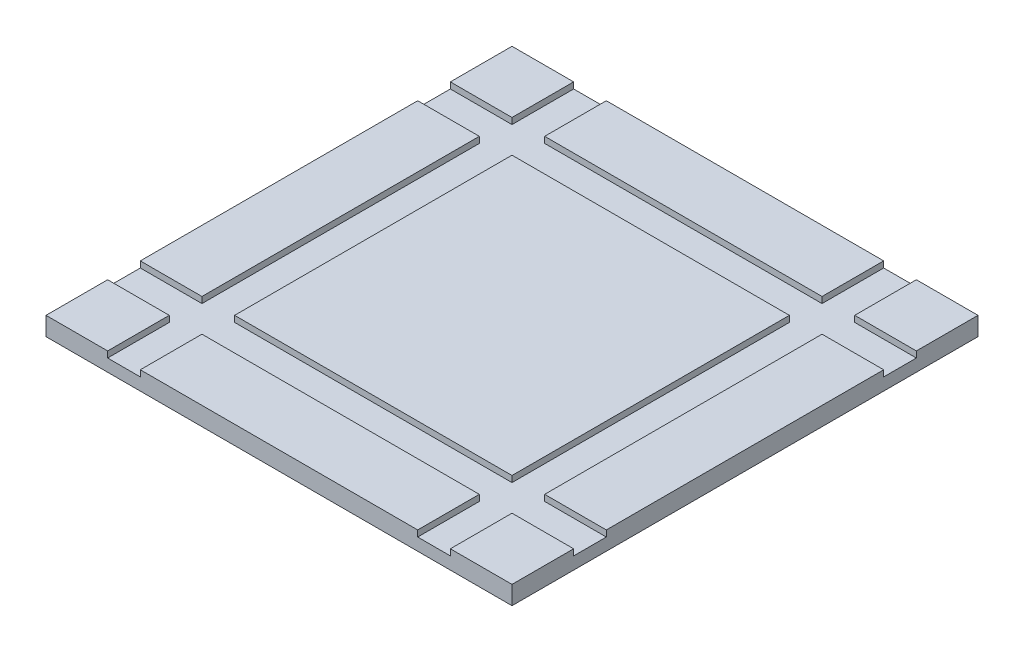
SolidWorks part; units mm, degrees
ref_plane "Front Plane" through (0, 0, 0) normal (0, 0, 1) x (1, 0, 0)
ref_plane "Top Plane" through (0, 0, 0) normal (0, 1, 0) x (1, 0, 0)
ref_plane "Right Plane" through (0, 0, 0) normal (1, 0, 0) x (0, 0, -1)
sketch "Sketch1" plane through (0, 0, 0) normal (0, 1, 0) x (1, 0, 0)
  line L0 (-37.8, 22.5) -> (-37.8, 27.8)
  line L5 (-37.8, 37.8) -> (-27.8, 37.8)
  line L6 (-37.8, 37.8) -> (-37.8, 27.8)
  line L7 (-37.8, 27.8) -> (-27.8, 27.8)
  line L8 (-27.8, 37.8) -> (-27.8, 27.8)
  line L9 (-22.5, 22.5) -> (22.5, 22.5)
  line L10 (-22.5, 22.5) -> (-22.5, -22.5)
  line L11 (-22.5, -22.5) -> (22.5, -22.5)
  line L12 (22.5, 22.5) -> (22.5, -22.5)
  line L13 (-22.5, 27.8) -> (22.5, 27.8)
  line L14 (-22.5, 27.8) -> (-22.5, 37.8)
  line L15 (-22.5, 37.8) -> (22.5, 37.8)
  line L16 (22.5, 27.8) -> (22.5, 37.8)
  line L17 (27.8, 37.8) -> (37.8, 37.8)
  line L18 (27.8, 37.8) -> (27.8, 27.8)
  line L19 (27.8, 27.8) -> (37.8, 27.8)
  line L20 (37.8, 37.8) -> (37.8, 27.8)
  line L21 (37.8, 22.5) -> (27.8, 22.5)
  line L22 (37.8, 22.5) -> (37.8, -22.5)
  line L23 (37.8, -22.5) -> (27.8, -22.5)
  line L24 (27.8, 22.5) -> (27.8, -22.5)
  line L25 (27.8, -27.8) -> (37.8, -27.8)
  line L26 (27.8, -27.8) -> (27.8, -37.8)
  line L27 (27.8, -37.8) -> (37.8, -37.8)
  line L28 (37.8, -27.8) -> (37.8, -37.8)
  line L29 (22.5, -27.8) -> (-22.5, -27.8)
  line L30 (22.5, -27.8) -> (22.5, -37.8)
  line L31 (22.5, -37.8) -> (-22.5, -37.8)
  line L32 (-22.5, -27.8) -> (-22.5, -37.8)
  line L33 (-27.8, -27.8) -> (-37.8, -27.8)
  line L34 (-27.8, -27.8) -> (-27.8, -37.8)
  line L35 (-27.8, -37.8) -> (-37.8, -37.8)
  line L36 (-37.8, -27.8) -> (-37.8, -37.8)
  line L37 (-37.8, -22.5) -> (-27.8, -22.5)
  line L38 (-37.8, -22.5) -> (-37.8, 22.5)
  line L39 (-37.8, 22.5) -> (-27.8, 22.5)
  line L40 (-27.8, -22.5) -> (-27.8, 22.5)
  line L41 (-27.8, 37.8) -> (-22.5, 37.8)
  line L42 (22.5, 37.8) -> (27.8, 37.8)
  line L43 (37.8, 27.8) -> (37.8, 22.5)
  line L44 (37.8, -22.5) -> (37.8, -27.8)
  line L45 (27.8, -37.8) -> (22.5, -37.8)
  line L46 (-22.5, -37.8) -> (-27.8, -37.8)
  line L47 (-37.8, -27.8) -> (-37.8, -22.5)
  point P37 (22.5, 0)
  point P38 (0, 22.5)
  dimension "D1" = 22.5
  dimension "D2" = 5.3
  dimension "D3" = 10
extrude "Boss-Extrude1" add sketch "Sketch1" against normal blind 2 contours L47 L33 L34 L46 L32 L29 L30 L45 L26 L25 L44 L23 L24 L21 L43 L19 L18 L42 L16 L13 L14 L41 L8 L7 L0 L39 L40 L37 L9 L12 L11 L10 | L37 L40 L39 L38 | L33 L36 L35 L34 | L29 L32 L31 L30 | L28 L25 L26 L27 | L21 L24 L23 L22 | L12 L9 L10 L11 | L13 L16 L15 L14 | L20 L17 L18 L19 | L8 L5 L6 L7 region at (-32.8, 0, 0) region at (-36.7309, 0, -25.15) region at (-32.8, 0, -32.8) region at (-32.8, 0, 32.8) region at (0, 0, -32.8) region at (0, 0, 32.8) region at (32.8, 0, -32.8) region at (32.8, 0, 32.8) region at (32.8, 0, 0) region at (0, 0, 0)
extrude "Boss-Extrude2" add sketch "Sketch1<3>" along normal blind 1 contours L33 L36 L35 L34 | L37 L40 L39 L38 | L8 L5 L6 L7 | L13 L16 L15 L14 | L20 L17 L18 L19 | L21 L24 L23 L22 | L28 L25 L26 L27 | L29 L32 L31 L30 | L12 L9 L10 L11 region at (-32.8, 0, 0) region at (-32.8, 0, -32.8) region at (-32.8, 0, 32.8) region at (0, 0, -32.8) region at (0, 0, 32.8) region at (32.8, 0, -32.8) region at (32.8, 0, 32.8) region at (32.8, 0, 0) region at (0, 0, 0)
sketch "Sketch1<3>" plane through (0, 0, 0) normal (0, 1, 0) x (1, 0, 0) same geometry as "Sketch1"
